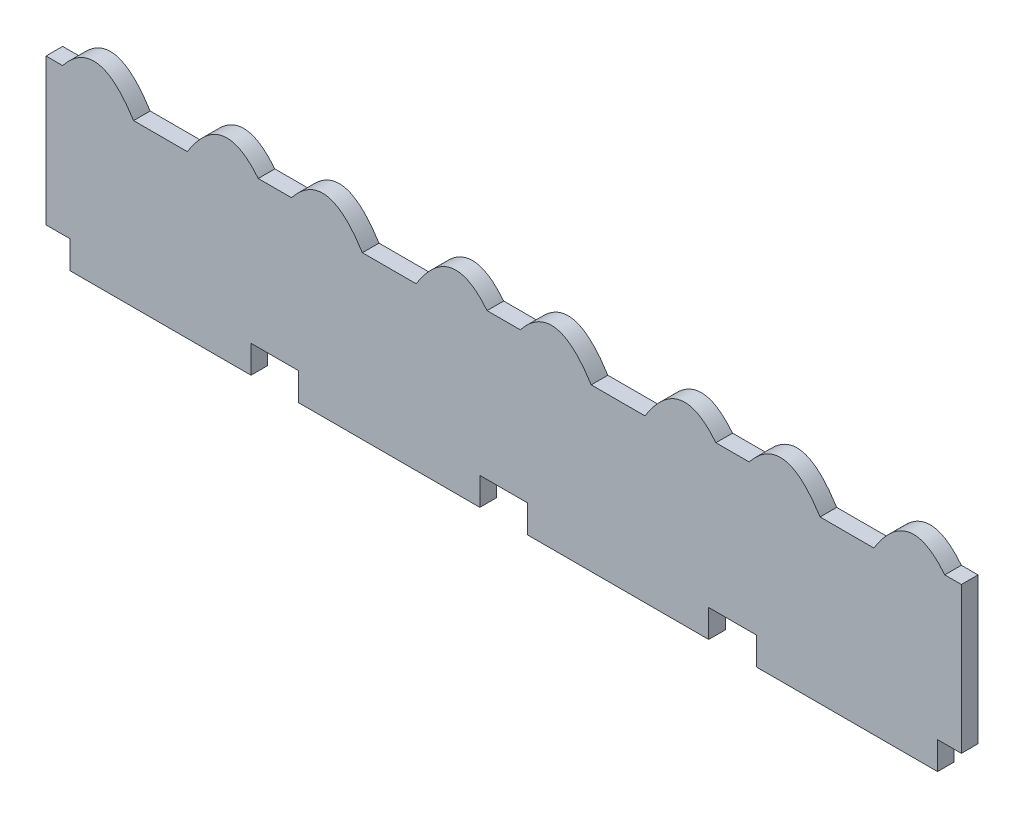
SolidWorks part; units mm, degrees
material "PP Copolymer"
ref_plane "Front Plane" through (0, 0, 0) normal (0, 0, 1) x (1, 0, 0)
ref_plane "Top Plane" through (0, 0, 0) normal (0, 1, 0) x (1, 0, 0)
ref_plane "Right Plane" through (0, 0, 0) normal (1, 0, 0) x (0, 0, -1)
sketch "Sketch1" plane through (0, 0, 0) normal (0, 0, 1) x (1, 0, 0)
  line L0 (70.775, 15.7) -> (72.275, 15.7) construction
  line L1 (59.525, 14.6) -> (64.375, 14.6) construction
  line L2 (51.625, 15.7) -> (53.125, 15.7) construction
  line L3 (50.125, 15.7) -> (51.625, 15.7) construction
  line L4 (38.875, 14.6) -> (43.725, 14.6) construction
  line L5 (30.975, 15.7) -> (32.475, 15.7) construction
  line L6 (29.475, 15.7) -> (30.975, 15.7) construction
  line L7 (18.225, 14.6) -> (23.075, 14.6) construction
  line L8 (10.325, 15.7) -> (11.825, 15.7) construction
  line L9 (8.825, 15.7) -> (10.325, 15.7) construction
  line L10 (-2.425, 14.6) -> (2.425, 14.6) construction
  line L11 (-10.325, 15.7) -> (-8.825, 15.7) construction
  line L12 (72.275, 15.7) -> (72.275, 2.5) construction
  line L13 (72.275, 2.5) -> (70.125, 2.5) construction
  line L14 (70.125, 2.5) -> (70.125, 0) construction
  line L15 (70.125, 0) -> (53.775, 0) construction
  line L16 (53.775, 0) -> (53.775, 2.5) construction
  line L17 (53.775, 2.5) -> (51.625, 2.5) construction
  line L18 (51.625, 2.5) -> (49.475, 2.5) construction
  line L19 (49.475, 0) -> (33.125, 0) construction
  line L20 (33.125, 0) -> (33.125, 2.5) construction
  line L21 (33.125, 2.5) -> (30.975, 2.5) construction
  line L22 (30.975, 2.5) -> (28.825, 2.5) construction
  line L23 (28.825, 2.5) -> (28.825, 0) construction
  line L24 (28.825, 0) -> (12.475, 0) construction
  line L25 (12.475, 0) -> (12.475, 2.5) construction
  line L26 (12.475, 2.5) -> (10.325, 2.5) construction
  line L27 (10.325, 2.5) -> (8.175, 2.5) construction
  line L28 (8.175, 2.5) -> (8.175, 0) construction
  line L29 (8.175, 0) -> (-8.175, 0) construction
  line L30 (-8.175, 0) -> (-8.175, 2.5) construction
  line L31 (-8.175, 2.5) -> (-10.325, 2.5) construction
  line L32 (-10.325, 2.5) -> (-10.325, 15.7) construction
  line L33 (70.775, 15.7) -> (72.275, 15.7)
  line L34 (59.525, 14.6) -> (64.375, 14.6)
  line L35 (51.625, 15.7) -> (53.125, 15.7)
  line L36 (50.125, 15.7) -> (51.625, 15.7)
  line L37 (38.875, 14.6) -> (43.725, 14.6)
  line L38 (30.975, 15.7) -> (32.475, 15.7)
  line L39 (29.475, 15.7) -> (30.975, 15.7)
  line L40 (18.225, 14.6) -> (23.075, 14.6)
  line L41 (10.325, 15.7) -> (11.825, 15.7)
  line L42 (8.825, 15.7) -> (10.325, 15.7)
  line L43 (-2.425, 14.6) -> (2.425, 14.6)
  line L44 (-10.325, 15.7) -> (-8.825, 15.7)
  line L45 (72.275, 15.7) -> (72.275, 2.5)
  line L46 (72.275, 2.5) -> (70.125, 2.5)
  line L47 (70.125, 2.5) -> (70.125, 0)
  line L48 (70.125, 0) -> (53.775, 0)
  line L49 (53.775, 0) -> (53.775, 2.5)
  line L50 (53.775, 2.5) -> (51.625, 2.5)
  line L51 (51.625, 2.5) -> (49.475, 2.5)
  line L52 (49.475, 0) -> (33.125, 0)
  line L53 (33.125, 0) -> (33.125, 2.5)
  line L54 (33.125, 2.5) -> (30.975, 2.5)
  line L55 (30.975, 2.5) -> (28.825, 2.5)
  line L56 (28.825, 2.5) -> (28.825, 0)
  line L57 (28.825, 0) -> (12.475, 0)
  line L58 (12.475, 0) -> (12.475, 2.5)
  line L59 (12.475, 2.5) -> (10.325, 2.5)
  line L60 (10.325, 2.5) -> (8.175, 2.5)
  line L61 (8.175, 2.5) -> (8.175, 0)
  line L62 (8.175, 0) -> (-8.175, 0)
  line L63 (-8.175, 0) -> (-8.175, 2.5)
  line L64 (-8.175, 2.5) -> (-10.325, 2.5)
  line L65 (-10.325, 2.5) -> (-10.325, 15.7)
  line L66 (49.475, 2.5) -> (49.475, 0) construction
  line L67 (49.475, 2.5) -> (49.475, 0)
  parabola Q0 (64.375, 14.6) -> (70.775, 15.7) focus (67.9615, 16.3356) apex (67.9615, 17.46) construction
  parabola Q1 (53.125, 15.7) -> (59.525, 14.6) focus (55.9385, 16.3356) apex (55.9385, 17.46) construction
  parabola Q2 (43.725, 14.6) -> (50.125, 15.7) focus (47.3115, 16.3356) apex (47.3115, 17.46) construction
  parabola Q3 (32.475, 15.7) -> (38.875, 14.6) focus (35.2885, 16.3356) apex (35.2885, 17.46) construction
  parabola Q4 (23.075, 14.6) -> (29.475, 15.7) focus (26.6615, 16.3356) apex (26.6615, 17.46) construction
  parabola Q5 (11.825, 15.7) -> (18.225, 14.6) focus (14.6385, 16.3356) apex (14.6385, 17.46) construction
  parabola Q6 (2.425, 14.6) -> (8.825, 15.7) focus (6.0115, 16.3356) apex (6.0115, 17.46) construction
  parabola Q7 (-8.825, 15.7) -> (-2.425, 14.6) focus (-6.0115, 16.3356) apex (-6.0115, 17.46) construction
  parabola Q8 (64.375, 14.6) -> (70.775, 15.7) focus (67.9615, 16.3356) apex (67.9615, 17.46)
  parabola Q9 (53.125, 15.7) -> (59.525, 14.6) focus (55.9385, 16.3356) apex (55.9385, 17.46)
  parabola Q10 (43.725, 14.6) -> (50.125, 15.7) focus (47.3115, 16.3356) apex (47.3115, 17.46)
  parabola Q11 (32.475, 15.7) -> (38.875, 14.6) focus (35.2885, 16.3356) apex (35.2885, 17.46)
  parabola Q12 (23.075, 14.6) -> (29.475, 15.7) focus (26.6615, 16.3356) apex (26.6615, 17.46)
  parabola Q13 (11.825, 15.7) -> (18.225, 14.6) focus (14.6385, 16.3356) apex (14.6385, 17.46)
  parabola Q14 (2.425, 14.6) -> (8.825, 15.7) focus (6.0115, 16.3356) apex (6.0115, 17.46)
  parabola Q15 (-8.825, 15.7) -> (-2.425, 14.6) focus (-6.0115, 16.3356) apex (-6.0115, 17.46)
extrude "Extrude1" add sketch "Sketch1" along normal blind 1.5
sketch "Sketch2" plane through (72.275, 0, 0) normal (1, 0, 0) x (0, 0, -1)
  line L0 (-2.2, 8.5) -> (-2.2, 4.6) construction
  line L1 (-1.5, 2.5) -> (-1.5, 15.7) construction
  line L2 (0, 0) -> (78, 0) construction
  circle A0 centre (-2.2, 8.5) radius 1.25
  circle A1 centre (-2.2, 4.6) radius 1.25
  dimension "D1" = 2.5
  dimension "D2" = 0.7
  dimension "D3" = 4.6
  dimension "D4" = 8.5
extrude "Extrude2" [suppressed] add sketch "Sketch2" along normal blind 6 and the other way blind 4
